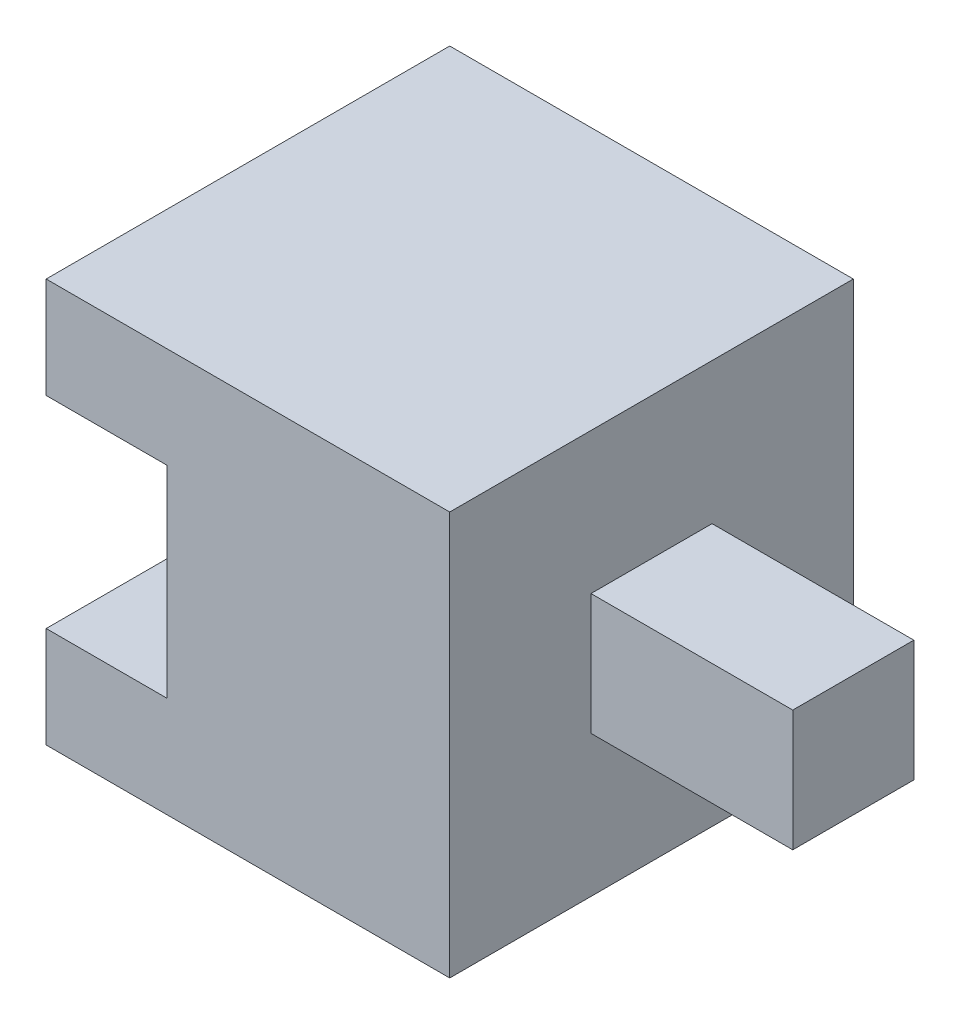
SolidWorks part; units mm, degrees
ref_plane "Front Plane" through (0, 0, 0) normal (0, 0, 1) x (1, 0, 0)
ref_plane "Top Plane" through (0, 0, 0) normal (0, 1, 0) x (1, 0, 0)
ref_plane "Right Plane" through (0, 0, 0) normal (1, 0, 0) x (0, 0, -1)
sketch "Sketch1" plane through (0, 0, 0) normal (0, 1, 0) x (1, 0, 0)
  line L1 (-5, -5) -> (5, -5)
  line L2 (-5, -5) -> (-5, 5)
  line L3 (-5, 5) -> (5, 5)
  line L4 (5, -5) -> (5, 5)
  line L5 (-5, -5) -> (5, 5) construction
  line L6 (-5, 5) -> (5, -5) construction
  point P0 (0, 0)
  dimension "D1" = 10
  dimension "D2" = 10
extrude "Boss-Extrude1" add sketch "Sketch1" along normal mid plane 10
sketch "Sketch2" plane through (0, 0, 5) normal (0, 0, 1) x (1, 0, 0)
  line L0 (-7.1123, 0) -> (7.1123, 0) construction
  line L1 (-5, 5) -> (-5, -5) construction
  line L2 (-2, -2.5) -> (-5, -2.5)
  line L3 (-2, -2.5) -> (-2, 2.5)
  line L4 (-2, 2.5) -> (-5, 2.5)
  line L5 (-5, -2.5) -> (-5, 2.5)
  line L6 (-2, -2.5) -> (-5, 2.5) construction
  line L7 (-2, 2.5) -> (-5, -2.5) construction
  point P0 (-3.5, 0)
  point P4 (0, 0)
  dimension "D1" = 3
  dimension "D2" = 5
extrude "Cut-Extrude1" cut sketch "Sketch2" against normal through all
sketch "Sketch3" plane through (5, 0, 0) normal (1, 0, 0) x (0, 0, -1)
  line L1 (-1.5, -1.5) -> (1.5, -1.5)
  line L2 (-1.5, -1.5) -> (-1.5, 1.5)
  line L3 (-1.5, 1.5) -> (1.5, 1.5)
  line L4 (1.5, -1.5) -> (1.5, 1.5)
  line L5 (-1.5, -1.5) -> (1.5, 1.5) construction
  line L6 (-1.5, 1.5) -> (1.5, -1.5) construction
  point P0 (0, 0)
  dimension "D1" = 3
  dimension "D2" = 3
extrude "Boss-Extrude2" add sketch "Sketch3" along normal blind 5
